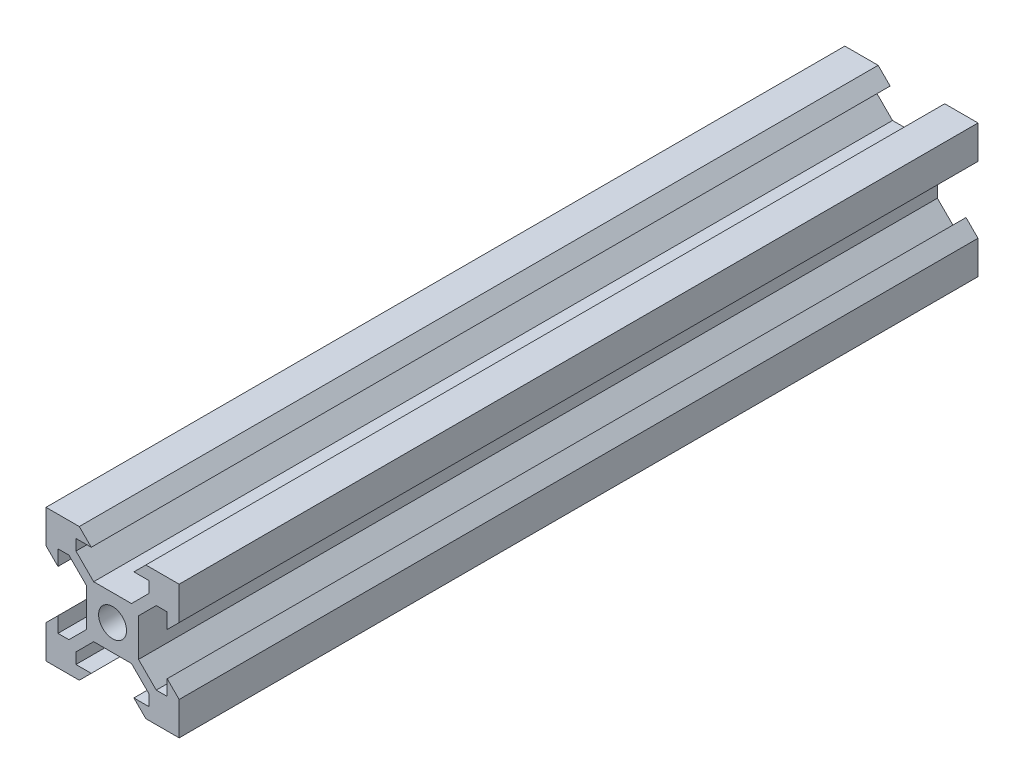
SolidWorks part; units mm, degrees
material "6063-T5"
ref_plane "Front Plane" through (0, 0, 0) normal (0, 0, 1) x (1, 0, 0)
ref_plane "Top Plane" through (0, 0, 0) normal (0, 1, 0) x (1, 0, 0)
ref_plane "Right Plane" through (0, 0, 0) normal (1, 0, 0) x (0, 0, -1)
sketch "Sketch1" plane through (0, 0, 0) normal (0, 0, 1) x (1, 0, 0)
  line L0 (-10, 10) -> (-5, 10)
  line L1 (10, -10) -> (-10, -10) construction
  line L2 (10, -10) -> (10, 10) construction
  line L3 (10, 10) -> (-10, 10) construction
  line L4 (-10, -10) -> (-10, 10) construction
  line L5 (10, -10) -> (-10, 10) construction
  line L6 (10, 10) -> (-10, -10) construction
  line L7 (-5, 10) -> (-3.2, 8.2)
  line L8 (-3.2, 8.2) -> (-5.4993, 8.2)
  line L9 (-5.4993, 8.2) -> (-5.4993, 6.56)
  line L10 (-2.84, 3.9007) -> (2.84, 3.9007)
  line L11 (0, 3.9007) -> (0, 2.1) construction
  line L12 (-5.4993, 6.56) -> (-2.84, 3.9007)
  line L13 (0, 0) -> (0, -13.2939) construction
  line L14 (0, 0) -> (-17.0802, 0) construction
  line L15 (-10, 10) -> (-10, 5)
  line L16 (-10, 5) -> (-8.2, 3.2)
  line L17 (-8.2, 3.2) -> (-8.2, 5.4993)
  line L18 (-8.2, 5.4993) -> (-6.56, 5.4993)
  line L19 (-6.56, 5.4993) -> (-3.9007, 2.84)
  line L20 (-3.9007, 2.84) -> (-3.9007, -2.84)
  line L21 (-3.2, -8.2) -> (-5.4993, -8.2)
  line L22 (-5.4993, -8.2) -> (-5.4993, -6.56)
  line L23 (-5, -10) -> (-3.2, -8.2)
  line L24 (-10, -10) -> (-5, -10)
  line L25 (-10, -10) -> (-10, -5)
  line L26 (-10, -5) -> (-8.2, -3.2)
  line L27 (-8.2, -3.2) -> (-8.2, -5.4993)
  line L28 (-8.2, -5.4993) -> (-6.56, -5.4993)
  line L29 (-6.56, -5.4993) -> (-3.9007, -2.84)
  line L30 (-5.4993, -6.56) -> (-2.84, -3.9007)
  line L31 (-2.84, -3.9007) -> (2.84, -3.9007)
  line L32 (5.4993, 6.56) -> (2.84, 3.9007)
  line L33 (3.2, 8.2) -> (5.4993, 8.2)
  line L34 (5.4993, 8.2) -> (5.4993, 6.56)
  line L35 (5, 10) -> (3.2, 8.2)
  line L36 (10, 10) -> (5, 10)
  line L37 (10, 10) -> (10, 5)
  line L38 (10, 5) -> (8.2, 3.2)
  line L39 (8.2, 3.2) -> (8.2, 5.4993)
  line L40 (8.2, 5.4993) -> (6.56, 5.4993)
  line L41 (6.56, 5.4993) -> (3.9007, 2.84)
  line L42 (3.9007, 2.84) -> (3.9007, -2.84)
  line L43 (6.56, -5.4993) -> (3.9007, -2.84)
  line L44 (8.2, -5.4993) -> (6.56, -5.4993)
  line L45 (8.2, -3.2) -> (8.2, -5.4993)
  line L46 (10, -5) -> (8.2, -3.2)
  line L47 (10, -10) -> (10, -5)
  line L48 (10, -10) -> (5, -10)
  line L49 (5, -10) -> (3.2, -8.2)
  line L50 (3.2, -8.2) -> (5.4993, -8.2)
  line L51 (5.4993, -8.2) -> (5.4993, -6.56)
  line L52 (5.4993, -6.56) -> (2.84, -3.9007)
  circle A0 centre (0, 0) radius 2.1
  arc A1 (0, -2.1) -> (0, 2.1) centre (0, 0) cw construction
  point P0 (0, 0)
  point P25 (-3.9007, 0)
  point P35 (0, 0)
  point P56 (0, -3.9007)
  dimension "D2" = 4.2
  dimension "D1" = 20
  dimension "D3" = 1.64
  dimension "D4" = 1.8
  dimension "D5" = 45
  dimension "D6" = 1.5
  dimension "D7" = 5.68
  dimension "D8" = 5
extrude "Boss-Extrude1" add sketch "Sketch1" along normal mid plane 120
